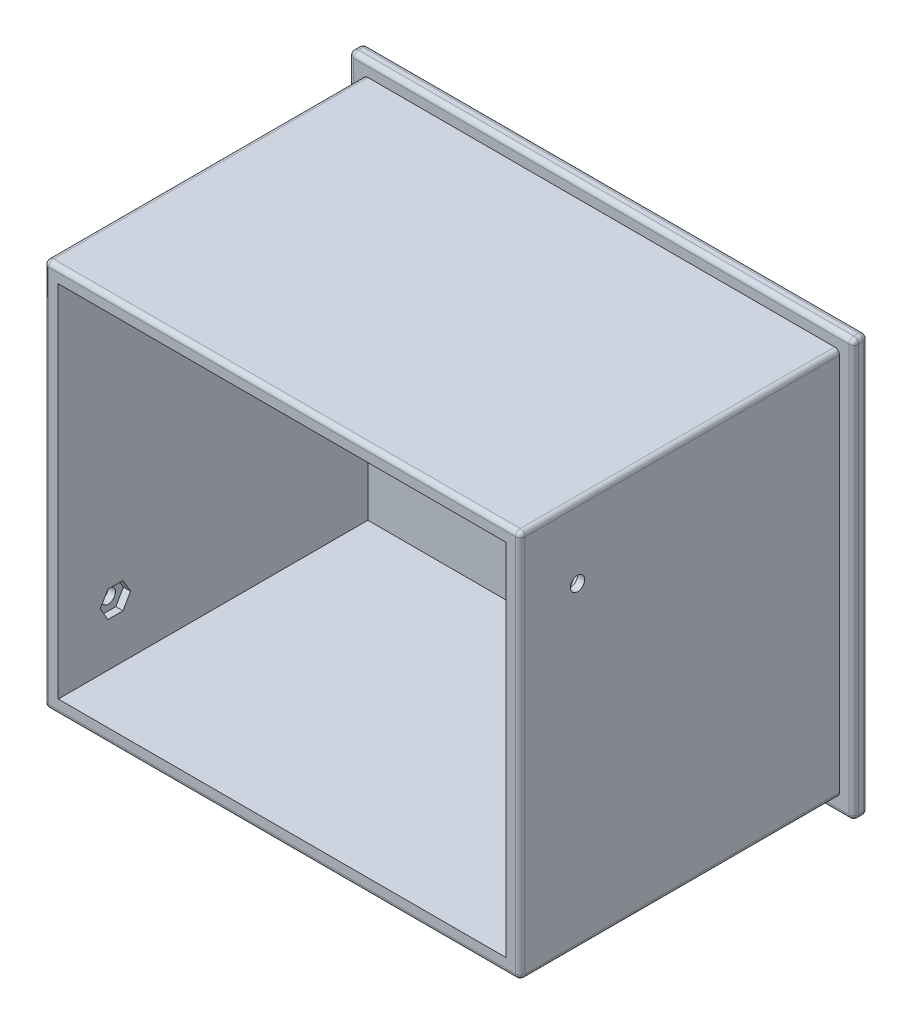
SolidWorks part; units mm, degrees
ref_plane "Plan de face" through (0, 0, 0) normal (0, 0, 1) x (1, 0, 0)
ref_plane "Plan de dessus" through (0, 0, 0) normal (0, 1, 0) x (1, 0, 0)
ref_plane "Plan de droite" through (0, 0, 0) normal (1, 0, 0) x (0, 0, -1)
sketch "Esquisse1" plane through (0, 0, 0) normal (0, 0, 1) x (1, 0, 0)
  line L20 (-105.377, -71.155) -> (-5.377, -71.155)
  line L21 (-105.377, -71.155) -> (-105.377, 10.345)
  line L22 (-105.377, 10.345) -> (-5.377, 10.345)
  line L23 (-5.377, -71.155) -> (-5.377, 10.345)
  line L32 (-108.377, -74.155) -> (-2.377, -74.155)
  line L33 (-108.377, -74.155) -> (-108.377, 13.345)
  line L34 (-108.377, 13.345) -> (-2.377, 13.345)
  line L35 (-2.377, -74.155) -> (-2.377, 13.345)
  line L36 (-102.377, 7.345) -> (-8.377, 7.345)
  line L37 (-102.377, 7.345) -> (-102.377, -68.155)
  line L38 (-102.377, -68.155) -> (-8.377, -68.155)
  line L39 (-8.377, 7.345) -> (-8.377, -68.155)
  dimension "D1" = 3
  dimension "D4" = 3
  dimension "D5" = 81.5
  dimension "D25" = 100
  dimension "D27" = 3
  dimension "D28" = 3
  dimension "D29" = 3
  dimension "D30" = 3
  dimension "D31" = 3
extrude "Boss.-Extru.1" add sketch "Esquisse1" along normal blind 3 contours L32 L35 L34 L33 L23 L20 L21 L22 region at (-107.0025, -30.405, 0)
extrude "Boss.-Extru.2" add sketch "Esquisse1<32>" along normal blind 70 contours L20 L23 L22 L21 L36 L39 L38 L37 region at (-104.087, -30.405, 0)
sketch "Esquisse1<32>" plane through (0, 0, 0) normal (0, 0, 1) x (1, 0, 0) same geometry as "Esquisse1"
extrude "Boss.-Extru.3" add sketch "Esquisse1<33>" along normal blind 5 contours L39 L36 L37 L38 region at (-55.377, -30.405, 0)
sketch "Esquisse1<33>" plane through (0, 0, 0) normal (0, 0, 1) x (1, 0, 0) same geometry as "Esquisse1"
sketch "Esquisse11" plane through (-5.377, 0, 0) normal (1, 0, 0) x (0, 0, -1)
  line L0 (-70, 10.345) -> (-3, 10.345) construction
  line L1 (-54.8246, -4.655) -> (-56.4123, -1.905)
  line L2 (-56.4123, -1.905) -> (-59.5877, -1.905)
  line L3 (-59.5877, -1.905) -> (-61.1754, -4.655)
  line L4 (-61.1754, -4.655) -> (-59.5877, -7.405)
  line L5 (-59.5877, -7.405) -> (-56.4123, -7.405)
  line L6 (-56.4123, -7.405) -> (-54.8246, -4.655)
  line L8 (-70, -71.155) -> (-70, 10.345) construction
  circle A0 centre (-58, -4.655) radius 2.75 construction
  circle A1 centre (-58, -4.655) radius 1.5
  circle A2 centre (-58, -4.655) radius 5
  dimension "D1" = 5.5
  dimension "D2" = 15
  dimension "D3" = 12
sketch "Esquisse13" plane through (-105.377, 0, 0) normal (-1, 0, 0) x (0, 0, 1)
  line L0 (70, -71.155) -> (70, 10.345) construction
  line L1 (61.1754, -56.155) -> (59.5877, -53.405)
  line L2 (59.5877, -53.405) -> (56.4123, -53.405)
  line L3 (56.4123, -53.405) -> (54.8246, -56.155)
  line L4 (54.8246, -56.155) -> (56.4123, -58.905)
  line L5 (56.4123, -58.905) -> (59.5877, -58.905)
  line L6 (59.5877, -58.905) -> (61.1754, -56.155)
  line L8 (70, -71.155) -> (3, -71.155) construction
  circle A0 centre (58, -56.155) radius 2.75 construction
  circle A1 centre (58, -56.155) radius 4.4439
  circle A2 centre (58, -56.155) radius 1.5
  dimension "D1" = 5.5
  dimension "D2" = 12
  dimension "D3" = 15
fillet "Congé1" radius 1 4 edges at (-55.377, -71.155, 70) (-5.377, -30.405, 70) (-55.377, 10.345, 70) (-105.377, -30.405, 70)
fillet "Congé2" radius 1 4 edges at (-2.377, -30.405, 3) (-55.377, 13.345, 3) (-108.377, -30.405, 3) (-55.377, -74.155, 3)
sketch "Esquisse14" plane through (0, 0, 0) normal (0, 0, -1) x (-1, 0, 0)
fillet "Congé3" radius 1 12 edges at (-2.6699, 13.0521, 2.7071) (-108.0841, 13.0521, 2.7071) (-108.0841, -73.8621, 2.7071) (-2.6699, -73.8621, 2.7071) (-2.377, -30.405, 0) (-55.377, 13.345, 0) (-2.377, 13.345, 1) (-108.377, -30.405, 0) (-108.377, 13.345, 1) (-55.377, -74.155, 0) (-108.377, -74.155, 1) (-2.377, -74.155, 1)
extrude "Enlèv. mat.-Extru.1" cut sketch "Esquisse13" against normal blind 3 contours A2
extrude "Enlèv. mat.-Extru.2" cut sketch "Esquisse13<3>" against normal blind 3 contours L5 L6 L1 L2 L3 L4 A2 region at (-105.377, -57.488, 60.3088)
sketch "Esquisse13<3>" plane through (-105.377, 0, 0) normal (-1, 0, 0) x (0, 0, 1) same geometry as "Esquisse13"
extrude "Boss.-Extru.6" add sketch "Esquisse13<4>" against normal blind 1.5 contours L5 L6 L1 L2 L3 L4 A2 region at (-105.377, -57.488, 60.3088)
sketch "Esquisse13<4>" plane through (-105.377, 0, 0) normal (-1, 0, 0) x (0, 0, 1) same geometry as "Esquisse13"
extrude "Enlèv. mat.-Extru.6" cut sketch "Esquisse11" against normal blind 3 contours L5 L6 L1 L2 L3 L4 A1 | A1 region at (-5.377, -5.988, 55.6912) region at (-5.377, -4.655, 58)
extrude "Boss.-Extru.8" add sketch "Esquisse11<11>" against normal blind 1.5 contours A2 L6 L5 L4 L3 L2 L1 | L5 L6 L1 L2 L3 L4 A1 | A1 region at (-5.377, -5.988, 55.6912) region at (-5.377, -4.655, 58) region at (-5.377, -4.655, 62.8586)
sketch "Esquisse11<11>" plane through (-5.377, 0, 0) normal (1, 0, 0) x (0, 0, -1) same geometry as "Esquisse11"
extrude "Enlèv. mat.-Extru.7" cut sketch "Esquisse11<12>" against normal blind 1.5 contours A1 region at (-5.377, -4.655, 58)
sketch "Esquisse11<12>" plane through (-5.377, 0, 0) normal (1, 0, 0) x (0, 0, -1) same geometry as "Esquisse11"
fillet "Congé5" radius 1 8 edges at (-105.0841, 10.0521, 69.7071) (-5.6699, 10.0521, 69.7071) (-5.6699, -70.8621, 69.7071) (-105.0841, -70.8621, 69.7071) (-105.377, 10.345, 36) (-5.377, 10.345, 36) (-5.377, -71.155, 36) (-105.377, -71.155, 36)
